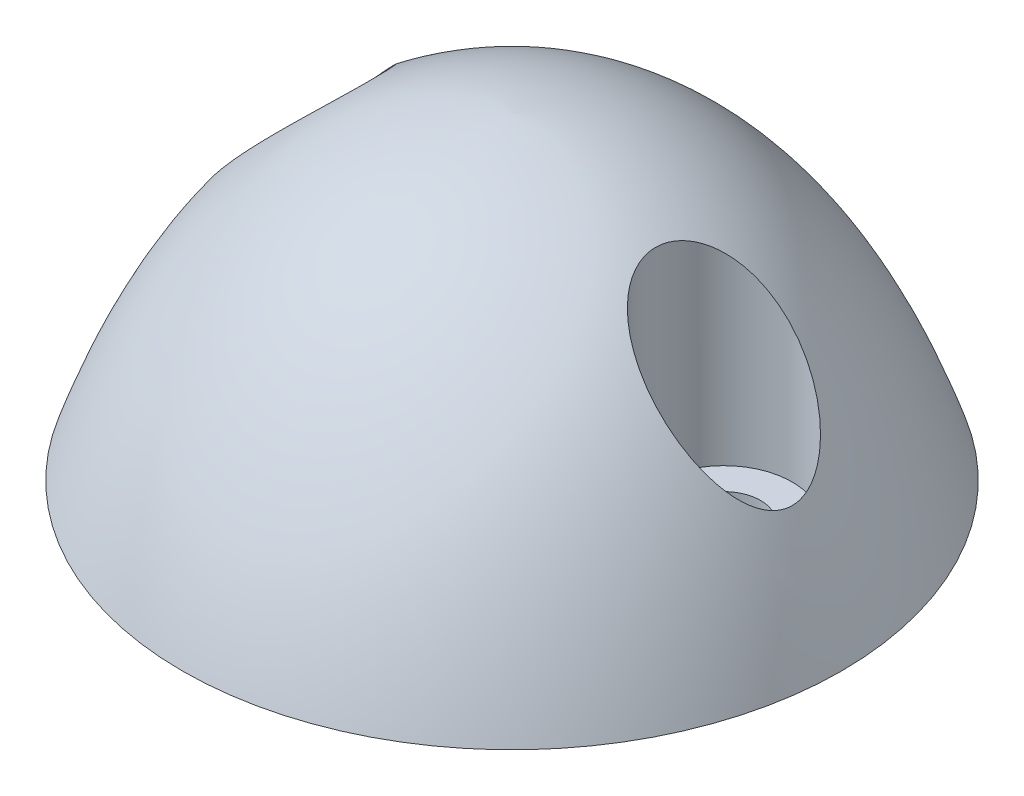
SolidWorks part; units mm, degrees
material "ABS"
ref_plane "Front Plane" through (0, 0, 0) normal (0, 0, 1) x (1, 0, 0)
ref_plane "Top Plane" through (0, 0, 0) normal (0, 1, 0) x (1, 0, 0)
ref_plane "Right Plane" through (0, 0, 0) normal (1, 0, 0) x (0, 0, -1)
sketch "Sketch1" plane through (0, 0, 0) normal (0, 0, 1) x (1, 0, 0)
  line L0 (12.5, 0) -> (14, 0)
  line L1 (0, 0.6223) -> (0, 13.5) construction
  line L2 (0, 13.5) -> (0, 12)
  spline S0 degree 3 poles (0, 12) (4.1774, 12.4646) (11.7263, 7.4899) (12.5, 0) knots 0 0 0 0 0.828663 0.828663 0.828663 0.828663
  spline S3 degree 2 poles (14, 0) (9.7543, 12.9509) (0, 13.5) knots 0 0 0 0.755787 0.755787 0.755787
  dimension "D3" = 12.5
  dimension "D1" = 1.5
  dimension "D2" = 14
  dimension "D4" = 12
revolve "Revolve1" add sketch "Sketch1" angle 360 about L2
sketch "Çizim1" plane through (0, 0, 0) normal (0, 1, 0) x (1, 0, 0)
  line L0 (0, -7.425) -> (0, 7.425) construction
  circle A0 centre (9, 0) radius 3
  circle A1 centre (-9, 0) radius 3
  dimension "D1" = 6
  dimension "9" = 9
extrude "Yükseklik-Ekstrüzyon2" add sketch "Çizim1" along normal up to surface (6.9952 mm away) up to face at (-12.5, 0, 0)
sketch "Çizim2" plane through (0, 0, 0) normal (0, 1, 0) x (1, 0, 0)
  line L0 (0, -7.425) -> (0, 7.425) construction
  circle A0 centre (9, 0) radius 1.55
  circle A1 centre (-9, 0) radius 1.55
  dimension "D1" = 3.1
extrude "Kes-Ekstrüzyon3" cut sketch "Çizim2" along normal blind 20
ref_plane "Düzlem1" through (0, 20, 0) normal (0, 1, 0) x (1, 0, 0)
sketch "Çizim3" plane through (0, 20, 0) normal (0, 1, 0) x (1, 0, 0)
  circle A4 centre (9, 0) radius 2.9
  circle A5 centre (-9, 0) radius 2.9
  dimension "D1" = 5.8
extrude "Kes-Ekstrüzyon4" cut sketch "Çizim3" against normal blind 17
